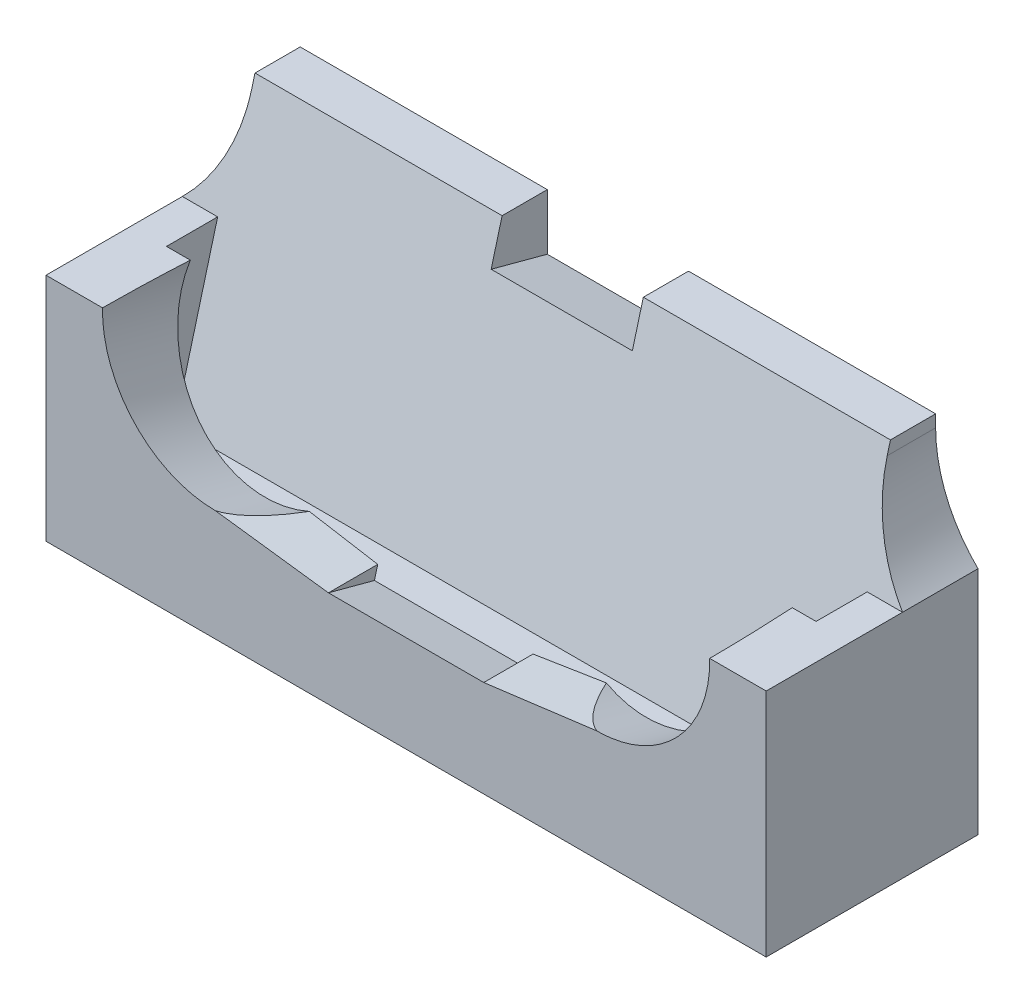
SolidWorks part; units mm, degrees
ref_plane "Front Plane" through (0, 0, 0) normal (0, 0, 1) x (1, 0, 0)
ref_plane "Top Plane" through (0, 0, 0) normal (0, 1, 0) x (1, 0, 0)
ref_plane "Right Plane" through (0, 0, 0) normal (1, 0, 0) x (0, 0, -1)
sketch "Sketch1" plane through (0, 0, 0) normal (0, 1, 0) x (1, 0, 0)
  line L1 (-21.375, 9.5455) -> (23.625, 9.5455)
  line L2 (-21.375, 9.5455) -> (-21.375, -5.4545)
  line L3 (-21.375, -5.4545) -> (23.625, -5.4545)
  line L4 (23.625, 9.5455) -> (23.625, -5.4545)
  dimension "D1" = 45
  dimension "D2" = 15
extrude "Boss-Extrude1" add sketch "Sketch1" along normal blind 5
sketch "Sketch2" plane through (23.625, 0, 0) normal (1, 0, 0) x (0, 0, -1)
  line L0 (-2.4545, 5) -> (2.7218, 24.3185)
  line L1 (-5.4545, 5) -> (9.5455, 5) construction
  line L2 (1.1689, 5) -> (6.3453, 24.3185)
  line L4 (9.5455, 5) -> (1.1689, 5)
  line L5 (-2.4545, 5) -> (-5.4545, 5)
  line L6 (-5.4545, 5) -> (-5.4545, 24.3185)
  line L7 (-5.4545, 24.3185) -> (2.7218, 24.3185)
  line L8 (9.5455, 5) -> (9.5455, 24.3185)
  line L9 (9.5455, 24.3185) -> (6.3453, 24.3185)
  dimension "D1" = 3.5
  dimension "D2" = 20
  dimension "D3" = 20
  dimension "D4" = 75
  dimension "D5" = 3
extrude "Boss-Extrude2" add sketch "Sketch2" against normal up to vertex (45 mm away) up to point (-21.375, 5, 5.4545)
sketch "Sketch5" plane through (0, 0.9486, 3.5401) normal (0, -0.2588, -0.9659) x (-1, 0, 0)
  line L0 (-14.625, 6.1943) -> (12.375, 6.1943)
  line L1 (21.375, 4.1943) -> (-23.625, 4.1943) construction
  line L2 (-23.625, 4.1943) -> (-23.625, 24.1943) construction
  circle A0 centre (-14.625, 14.1943) radius 8
  circle A1 centre (12.375, 14.1943) radius 8
  dimension "D1" = 16
  dimension "D2" = 16
  dimension "D3" = 27
  dimension "D4" = 2
  dimension "D5" = 9
extrude "Cut-Extrude1" cut sketch "Sketch5" against normal blind 10 contours A1 | A0 region at (-12.375, 14.6593, -0.1336) region at (14.625, 14.6593, -0.1336)
sketch "Sketch6" plane through (0, 0, 5.4545) normal (0, 0, 1) x (1, 0, 0)
  line L0 (23.625, 24.3185) -> (23.625, 0) construction
  line L1 (-21.375, 24.3185) -> (23.625, 24.3185)
  line L2 (-21.375, 24.3185) -> (-21.375, 16.3185)
  line L3 (-21.375, 16.3185) -> (23.625, 16.3185)
  line L4 (23.625, 24.3185) -> (23.625, 16.3185)
  point P5 (23.625, 16.1566)
  dimension "D1" = 8
extrude "Cut-Extrude2" cut sketch "Sketch6" against normal up to surface (8.1764 mm away) up to face at (-12.375, 22.3867, -2.2042)
sketch "Sketch7" plane through (0, 0.9486, 3.5401) normal (0, -0.2588, -0.9659) x (-1, 0, 0)
  line L1 (-6.625, 5.1943) -> (4.375, 5.1943)
  line L2 (-6.625, 5.1943) -> (-6.625, 15.9121)
  line L3 (-6.625, 15.9121) -> (4.375, 15.9121)
  line L4 (4.375, 5.1943) -> (4.375, 15.9121)
  line L6 (4.5616, 15.9121) -> (-6.8116, 15.9121) construction
  line L7 (21.375, 14.3507) -> (21.375, -1.4117) construction
  line L8 (21.375, 4.1943) -> (-23.625, 4.1943) construction
  dimension "D1" = 11
  dimension "D2" = 0
  dimension "D3" = 17
  dimension "D4" = 1
extrude "Cut-Extrude4" cut sketch "Sketch7" against normal blind 6.5
sketch "Sketch9" plane through (0, 0, 5.4545) normal (0, 0, 1) x (1, 0, 0)
  line L0 (-12.375, 7.8744) -> (-4.375, 6.8391)
  line L1 (6.625, 6.8391) -> (14.625, 7.8744)
  line L2 (6.625, 6.8391) -> (-4.375, 6.8391)
  line L3 (-12.375, 7.8744) -> (-12.375, 17.1427)
  line L4 (-12.375, 17.1427) -> (14.625, 17.1427)
  line L5 (14.625, 7.8744) -> (14.625, 17.1427)
  ellipse E0 centre (-12.375, 16.1566) end of major axis (-12.375, 7.8744) minor radius 8 (-20.3735, 16.3185) -> (-4.375, 16.1566) ccw construction
  ellipse E1 centre (14.625, 16.1566) end of major axis (14.625, 7.8744) minor radius 8 (6.625, 16.1566) -> (22.6235, 16.3185) ccw construction
extrude "Cut-Extrude5" cut sketch "Sketch9" against normal up to surface (3.7702 mm away) up to face at (1.125, 9.9501, 1.1282)
sketch "Sketch10" plane through (-21.375, 0, 0) normal (-1, 0, 0) x (0, 0, 1)
  line L1 (5.4545, 16.3185) -> (-9.5455, 16.3185)
  line L2 (5.4545, 16.3185) -> (5.4545, 0)
  line L3 (5.4545, 0) -> (-9.5455, 0)
  line L4 (-9.5455, 16.3185) -> (-9.5455, 0)
  point P5 (-9.5455, 0)
extrude "Boss-Extrude3" add sketch "Sketch10" along normal blind 3
sketch "Sketch11" plane through (23.625, 0, 0) normal (1, 0, 0) x (0, 0, -1)
  line L0 (9.5455, 24.3185) -> (9.5455, 0) construction
  line L1 (-5.4545, 16.3185) -> (9.5455, 16.3185)
  line L2 (-5.4545, 16.3185) -> (-5.4545, 0)
  line L3 (-5.4545, 0) -> (9.5455, 0)
  line L4 (9.5455, 16.3185) -> (9.5455, 0)
  line L5 (-5.4545, 0) -> (9.5455, 0) construction
  point P7 (-5.4545, 0)
extrude "Boss-Extrude4" add sketch "Sketch11" along normal blind 3
sketch "Sketch12" plane through (0, 0.0427, 0.1594) normal (0, 0.2588, 0.9659) x (1, 0, 0)
  line L0 (-21.375, 5.1322) -> (23.625, 5.1322) construction
  line L1 (-3.875, 29.8114) -> (6.125, 29.8114)
  line L2 (-3.875, 29.8114) -> (-3.875, 22.1322)
  line L3 (-3.875, 22.1322) -> (6.125, 22.1322)
  line L4 (6.125, 29.8114) -> (6.125, 22.1322)
  line L5 (23.625, 25.1322) -> (23.625, 16.85) construction
  line L6 (-21.375, 25.1322) -> (-21.375, 16.85) construction
  dimension "D1" = 10
  dimension "D2" = 17
  dimension "D3" = 17.5
  dimension "D4" = 17.5
extrude "Cut-Extrude6" cut sketch "Sketch12" against normal blind 6
fillet "Fillet1" radius 10 2 edges at (-21.375, 16.3185, -6.8736) (23.625, 16.3185, -6.8736)
sketch "Sketch14" plane through (-21.375, 0, 0) normal (1, 0, 0) x (0, 0, -1)
  line L0 (0.5782, 16.3185) -> (4.2017, 16.3185)
  line L1 (4.2017, 16.3185) -> (1.1689, 5)
  line L2 (1.1689, 5) -> (-2.4545, 5)
  line L3 (-2.4545, 5) -> (0.5782, 16.3185)
extrude "Cut-Extrude7" cut sketch "Sketch14" against normal blind 0.5
sketch "Sketch15" plane through (23.625, 0, 0) normal (-1, 0, 0) x (0, 0, 1)
  line L0 (-4.2017, 16.3185) -> (-0.5782, 16.3185)
  line L1 (-0.5782, 16.3185) -> (2.4545, 5)
  line L2 (2.4545, 5) -> (-1.1689, 5) construction
  line L3 (2.4545, 5) -> (-0.5782, 16.3185) construction
  line L4 (2.4545, 5) -> (-1.1689, 5)
  line L5 (-1.1689, 5) -> (-4.2017, 16.3185)
extrude "Cut-Extrude8" cut sketch "Sketch15" against normal blind 0.5
